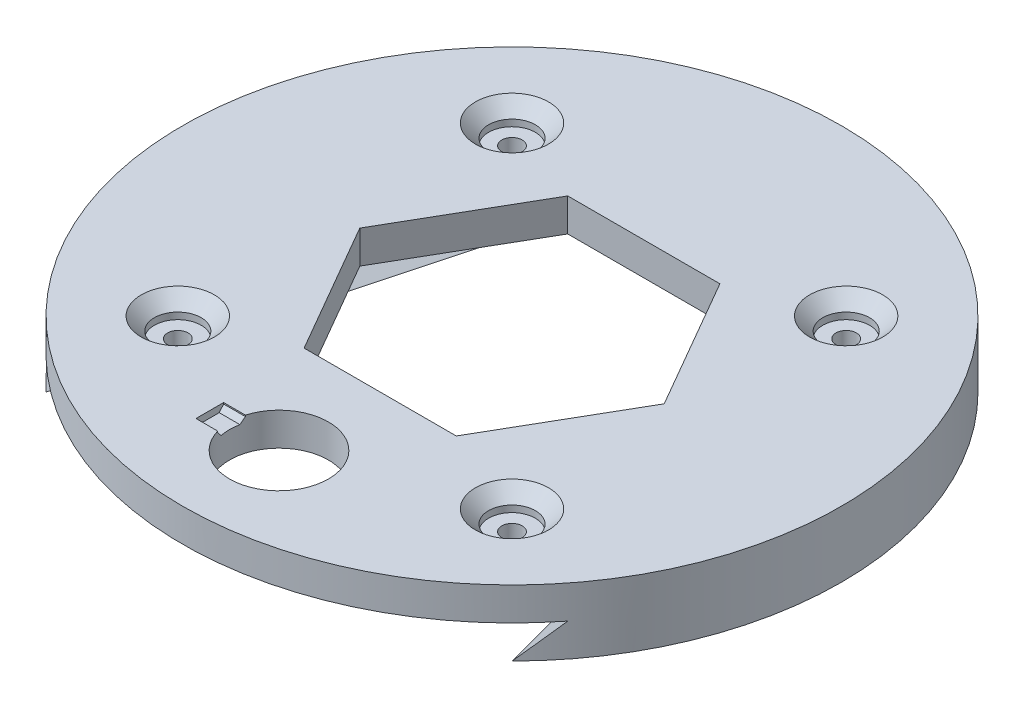
SolidWorks part; units mm, degrees
ref_plane "Front Plane" through (0, 0, 0) normal (0, 0, 1) x (1, 0, 0)
ref_plane "Top Plane" through (0, 0, 0) normal (0, 1, 0) x (1, 0, 0)
ref_plane "Right Plane" through (0, 0, 0) normal (1, 0, 0) x (0, 0, -1)
sketch "Sketch1" plane through (0, 0, 0) normal (0, 1, 0) x (1, 0, 0)
  line L0 (-35.3553, -35.3553) -> (-12.941, 48.2963)
  line L1 (-35.3553, -35.3553) -> (35.3553, -35.3553) construction
  line L2 (-35.3553, -35.3553) -> (-35.3553, 35.3553) construction
  line L3 (-35.3553, 35.3553) -> (35.3553, 35.3553) construction
  line L4 (35.3553, -35.3553) -> (35.3553, 35.3553) construction
  line L5 (-35.3553, -35.3553) -> (35.3553, 35.3553) construction
  line L6 (-35.3553, 35.3553) -> (35.3553, -35.3553) construction
  line L7 (0, 96.5926) -> (0, -94.4212) construction
  line L8 (35.3553, -35.3553) -> (12.941, 48.2963)
  circle A0 centre (0, 0) radius 50
  circle A1 centre (0, -35.3553) radius 7.5
  dimension "D1" = 100
  dimension "D3" = 15
  dimension "D2" = 15
extrude "Boss-Extrude1" add sketch "Sketch1" along normal blind 5 contours A0
extrude "Boss-Extrude2" add sketch "Sketch1<5>" against normal blind 5 contours L8 A0 | L0 A0 region at (-34.0499, 0, -9.1236) region at (34.0499, 0, -9.1236)
sketch "Sketch1<5>" plane through (0, 0, 0) normal (0, 1, 0) x (1, 0, 0) same geometry as "Sketch1"
draft "Draft1" type of draft neutral plane draft angle 45 faces to draft 2 face at (24.1481, -2.5, -6.4705) face at (-24.1481, -2.5, -6.4705) neutral plane through (0, -5, 0) neutral plane normal (0, -1, 0) reverse direction yes parameters "D1"=45
extrude "Cut-Extrude2" cut sketch "Sketch1<8>" against normal through all both and the other way through all contours A1 region at (0, 0, 35.3553)
sketch "Sketch1<8>" plane through (0, 0, 0) normal (0, 1, 0) x (1, 0, 0) same geometry as "Sketch1"
sketch "Sketch2" plane through (0, 0, 0) normal (0, -1, 0) x (1, 0, 0)
  line L1 (23.094, 0) -> (11.547, 20)
  line L2 (11.547, 20) -> (-11.547, 20)
  line L3 (-11.547, 20) -> (-23.094, 0)
  line L4 (-23.094, 0) -> (-11.547, -20)
  line L5 (-11.547, -20) -> (11.547, -20)
  line L6 (11.547, -20) -> (23.094, 0)
  circle A0 centre (0, 0) radius 20 construction
extrude "Cut-Extrude3" cut sketch "Sketch2" against normal through all
sketch "Sketch3" plane through (0, 5, 0) normal (0, 1, 0) x (1, 0, 0)
  line L0 (-25.3553, 25.3553) -> (25.3553, 25.3553) construction
  line L1 (-35.3553, 35.3553) -> (35.3553, 35.3553) construction
  line L2 (-35.3553, 35.3553) -> (-35.3553, -35.3553) construction
  line L3 (-35.3553, -35.3553) -> (35.3553, -35.3553) construction
  line L4 (35.3553, 35.3553) -> (35.3553, -35.3553) construction
  line L5 (-35.3553, 35.3553) -> (35.3553, -35.3553) construction
  line L6 (-35.3553, -35.3553) -> (35.3553, 35.3553) construction
  line L7 (25.3553, 25.3553) -> (25.3553, -25.3553) construction
  line L8 (-25.3553, -25.3553) -> (25.3553, -25.3553) construction
  line L9 (-25.3553, 25.3553) -> (-25.3553, -25.3553) construction
  circle A0 centre (0, 0) radius 50 construction
  circle A1 centre (-25.3553, 25.3553) radius 1.55
  circle A2 centre (-25.3553, 25.3553) radius 3.55
  circle A3 centre (25.3553, 25.3553) radius 1.55
  circle A4 centre (25.3553, 25.3553) radius 3.55
  circle A5 centre (25.3553, -25.3553) radius 1.55
  circle A6 centre (25.3553, -25.3553) radius 3.55
  circle A7 centre (-25.3553, -25.3553) radius 1.55
  circle A8 centre (-25.3553, -25.3553) radius 3.55
  point P0 (0, 0)
  point P30 (0, 0)
  dimension "D1" = 3.1
  dimension "D2" = 10
  dimension "D3" = 2
  dimension "D4" = 4
extrude "Cut-Extrude4" cut sketch "Sketch3" against normal blind 3
extrude "Cut-Extrude6" cut sketch "Sketch3<3>" against normal through all contours A7 | A1 | A3 | A5 region at (-25.3553, 5, 25.3553)
sketch "Sketch3<3>" plane through (0, 5, 0) normal (0, 1, 0) x (1, 0, 0) same geometry as "Sketch3"
chamfer "Chamfer1" distance 2 angle 45 4 edges at (25.3553, 5, -21.8053) (-25.3553, 5, -21.8053) (-25.3553, 5, 28.9053) (25.3553, 5, 28.9053)
sketch "Sketch4" plane through (0, 0, 0) normal (1, 0, 0) x (0, 0, -1)
  line L0 (-27.8553, 5) -> (-42.8553, 5) construction
  line L1 (-27.8553, 5) -> (-42.8553, 5) construction
  line L2 (-35.3553, 5) -> (-35.3553, 4) construction
  line L3 (-35.3553, 4) -> (-35.3553, 5.6) construction
  line L4 (-37.4553, 5.6) -> (-33.2553, 5.6)
  line L5 (-33.2553, 5.6) -> (-33.2553, 4.8)
  line L6 (-33.2553, 4.8) -> (-33.2553, 4.519) construction
  line L7 (-33.2553, 4.8) -> (-33.9266, 4)
  line L8 (-36.7841, 4) -> (-33.9266, 4)
  line L9 (-37.4553, 4.8) -> (-36.7841, 4)
  line L10 (-37.4553, 5.6) -> (-37.4553, 4.8)
  point P8 (-35.3553, 5.6)
  dimension "D1" = 1.6
  dimension "D2" = 4.2
  dimension "D3" = 1
  dimension "D4" = 0.8
  dimension "D5" = 40
extrude "Cut-Extrude7 - 3 + radius" cut sketch "Sketch4" against normal blind 10.5
